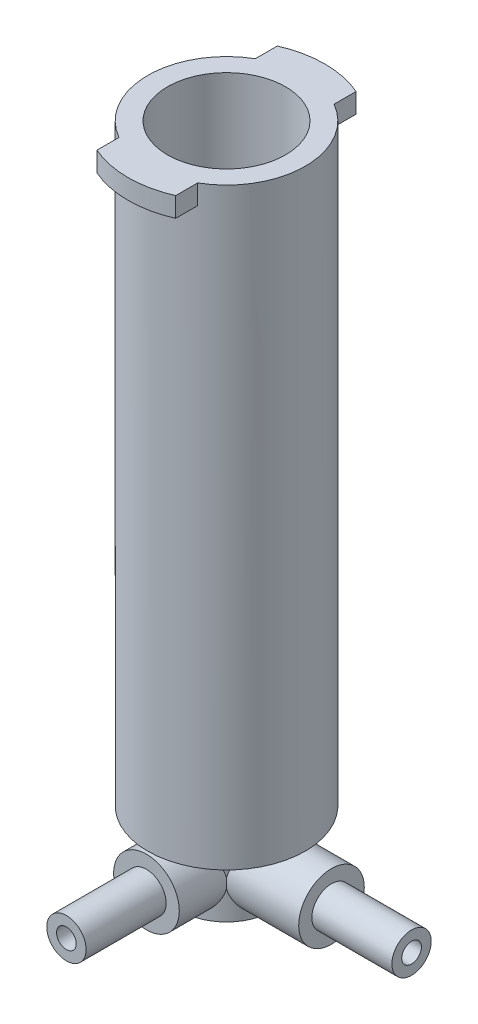
SolidWorks part; units mm, degrees
ref_plane "Front Plane" through (0, 0, 0) normal (0, 0, 1) x (1, 0, 0)
ref_plane "Top Plane" through (0, 0, 0) normal (0, 1, 0) x (1, 0, 0)
ref_plane "Right Plane" through (0, 0, 0) normal (1, 0, 0) x (0, 0, -1)
sketch "Sketch1" plane through (0, 0, 0) normal (0, 1, 0) x (1, 0, 0)
  circle A0 centre (0, 0) radius 6
extrude "Boss-Extrude1" add sketch "Sketch1" along normal blind 45.2 contours A0
shell "Shell1" thickness 1.5 removed face at (0, 45.2, 6)
sketch "Sketch2" plane through (0, 0, 0) normal (0, -1, 0) x (1, 0, 0)
  circle A0 centre (0, 0) radius 3.5
extrude "Boss-Extrude2" add sketch "Sketch2" along normal blind 5.2
shell "Shell2" thickness 1.5 removed face at (0, 1.5, 4.5)
sketch "Sketch3" plane through (0, 0, 0) normal (0, 0, 1) x (1, 0, 0)
  circle A0 centre (0, -2.6442) radius 2.5
extrude "Boss-Extrude3" add sketch "Sketch3" along normal blind 6.1
sketch "Sketch4" plane through (0, 0, 6.1) normal (0, 0, 1) x (1, 0, 0)
  circle A0 centre (0, -2.6442) radius 1.5
extrude "Boss-Extrude4" add sketch "Sketch4" along normal blind 6.1
sketch "Sketch5" plane through (0, 0, 12.2) normal (0, 0, 1) x (1, 0, 0)
  circle A0 centre (0, -2.6442) radius 0.75
extrude "Cut-Extrude1" cut sketch "Sketch5" against normal blind 12.1
sketch "Sketch6" plane through (0, -3.7, 0) normal (0, 1, 0) x (1, 0, 0)
  line L0 (2, 0) -> (-2, 0) construction
  circle A0 centre (0, 0) radius 2
extrude "Cut-Extrude2" cut sketch "Sketch6" along normal blind 12.1
sketch "Sketch7" plane through (0, 0, 0) normal (1, 0, 0) x (0, 0, -1)
  line L0 (0, 2.3996) -> (0, -6.384) construction
  line L1 (-6.1, -2.6442) -> (5.6134, -2.6442) construction
  line L2 (-6.1, -1.1442) -> (-6.1, -4.1442) construction
  circle A0 centre (0, -2.6442) radius 2.5
extrude "Boss-Extrude5" add sketch "Sketch7" along normal blind 8
sketch "Sketch8" plane through (8, 0, 0) normal (1, 0, 0) x (0, 0, -1)
  circle A0 centre (0, -2.6442) radius 1.5
extrude "Boss-Extrude6" add sketch "Sketch8" along normal blind 6.1
sketch "Sketch9" plane through (14.1, 0, 0) normal (1, 0, 0) x (0, 0, -1)
  circle A0 centre (0, -2.6442) radius 0.75
extrude "Cut-Extrude3" cut sketch "Sketch9" against normal blind 14.1
sketch "Sketch10" plane through (0, -3.7, 0) normal (0, 1, 0) x (1, 0, 0)
  circle A0 centre (0, 0) radius 2
extrude "Cut-Extrude4" cut sketch "Sketch10" along normal blind 14.1
sketch "Sketch11" plane through (0, 45.2, 0) normal (0, 1, 0) x (1, 0, 0)
  line L1 (3, -5.1962) -> (3, -6.8739)
  line L3 (-3, -5.1962) -> (-3, -6.8739)
  line L4 (-3, 5.1962) -> (-3, 6.8739)
  line L5 (3, 5.1962) -> (3, 6.8739)
  arc A0 (-3, -6.8739) -> (3, -6.8739) centre (0, 0) ccw
  arc A1 (-3, -5.1962) -> (3, -5.1962) centre (0, 0) ccw
  arc A2 (-3, 6.8739) -> (3, 6.8739) centre (0, 0) cw
  arc A3 (-3, 5.1962) -> (3, 5.1962) centre (0, 0) cw
extrude "Boss-Extrude7" add sketch "Sketch11" against normal blind 1.5
